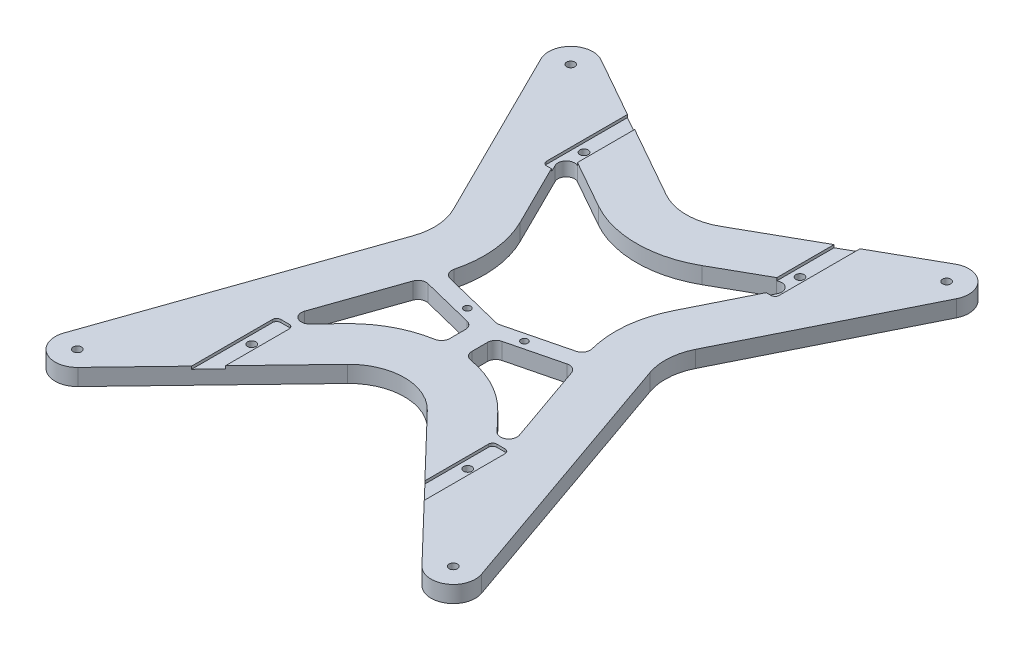
SolidWorks part; units mm, degrees
material "1060 Alloy"
ref_plane "Front Plane" through (0, 0, 0) normal (0, 0, 1) x (1, 0, 0)
ref_plane "Top Plane" through (0, 0, 0) normal (0, 1, 0) x (1, 0, 0)
ref_plane "Right Plane" through (0, 0, 0) normal (1, 0, 0) x (0, 0, -1)
sketch "Sketch1" plane through (0, 0, 0) normal (0, 1, 0) x (1, 0, 0)
  line L0 (-63.9527, 96.0638) -> (0, 60)
  line L1 (0, 60) -> (63.9527, 96.0638)
  line L2 (75.0466, 85.5357) -> (40, 15)
  line L3 (40, 15) -> (75.4349, -86.4576)
  line L4 (62.1139, -94.6385) -> (0, -30)
  line L5 (0, -30) -> (-62.1139, -94.6385)
  line L6 (-75.4349, -86.4576) -> (-40, 15)
  line L7 (-40, 15) -> (-75.0466, 85.5357)
  line L8 (-78.4889, 78.4889) -> (78.4889, -78.4889) construction
  line L9 (-42, 75) -> (-36, 75) construction
  line L10 (-42, 75) -> (-42, 55) construction
  line L11 (-42, 55) -> (-36, 55) construction
  line L12 (-36, 75) -> (-36, 55) construction
  line L13 (-42, 75) -> (-36, 55) construction
  line L14 (-42, 55) -> (-36, 75) construction
  line L15 (36, 75) -> (42, 75) construction
  line L16 (36, 75) -> (36, 55) construction
  line L17 (36, 55) -> (42, 55) construction
  line L18 (42, 75) -> (42, 55) construction
  line L19 (36, 75) -> (42, 55) construction
  line L20 (36, 55) -> (42, 75) construction
  line L21 (36, -45) -> (42, -45) construction
  line L22 (36, -45) -> (36, -65) construction
  line L23 (36, -65) -> (42, -65) construction
  line L24 (42, -45) -> (42, -65) construction
  line L25 (36, -45) -> (42, -65) construction
  line L26 (36, -65) -> (42, -45) construction
  line L27 (-42, -45) -> (-36, -45) construction
  line L28 (-42, -45) -> (-42, -65) construction
  line L29 (-42, -65) -> (-36, -65) construction
  line L30 (-36, -45) -> (-36, -65) construction
  line L31 (-42, -45) -> (-36, -65) construction
  line L32 (-42, -65) -> (-36, -45) construction
  line L33 (111, 45.9777) -> (45.9777, 111) construction
  line L34 (45.9777, 111) -> (-45.9777, 111) construction
  line L35 (-45.9777, 111) -> (-111, 45.9777) construction
  line L36 (-111, 45.9777) -> (-111, -45.9777) construction
  line L37 (-111, -45.9777) -> (-45.9777, -111) construction
  line L38 (-45.9777, -111) -> (45.9777, -111) construction
  line L39 (45.9777, -111) -> (111, -45.9777) construction
  line L40 (111, -45.9777) -> (111, 45.9777) construction
  line L41 (78.4889, 78.4889) -> (-78.4889, -78.4889) construction
  circle A0 centre (-67.8823, 89.0955) radius 1.5
  circle A1 centre (67.8823, 89.0955) radius 1.5
  circle A2 centre (-67.8823, -89.0955) radius 1.5
  circle A3 centre (67.8823, -89.0955) radius 1.5
  arc A4 (-63.9527, 96.0638) -> (-75.0466, 85.5357) centre (-67.8823, 89.0955) ccw
  arc A5 (63.9527, 96.0638) -> (75.0466, 85.5357) centre (67.8823, 89.0955) cw
  arc A6 (-75.4349, -86.4576) -> (-62.1139, -94.6385) centre (-67.8823, -89.0955) ccw
  arc A7 (75.4349, -86.4576) -> (62.1139, -94.6385) centre (67.8823, -89.0955) cw
  circle A8 centre (0, 0) radius 111 construction
  circle A9 centre (-39, 65) radius 1.5
  circle A10 centre (39, 65) radius 1.5
  circle A11 centre (39, -55) radius 1.5
  circle A12 centre (-39, -55) radius 1.5
  ellipse E0 centre (0, 15) end of major axis (0, 60) minor radius 40 construction
  dimension "D5" = 3
  dimension "D6" = 45
  dimension "D7" = 8
  dimension "D12" = 3
  dimension "D3" = 15
  dimension "D4" = 15
  dimension "D8" = 120
  dimension "D9" = 78
  dimension "D10" = 15
  dimension "D11" = 55
  dimension "D13" = 40
  dimension "D14" = 39
  dimension "D15" = 20
  dimension "D16" = 6
  dimension "D17" = 111
  dimension "D18" = 15
extrude "Boss-Extrude1" add sketch "Sketch1" along normal blind 6
fillet "Fillet1" radius 20 4 edges at (0, 3, -60) (-40, 3, -15) (0, 3, 30) (40, 3, -15)
sketch "Sketch2" plane through (0, 6, 0) normal (0, 1, 0) x (1, 0, 0)
  line L44 (-44.4448, 64.3983) -> (-27.6278, 30.5519)
  line L45 (-25.7837, 1.1137) -> (-43.3232, -49.1058)
  line L46 (-43.3232, -49.1058) -> (-27.3998, -32.5352)
  line L47 (27.3998, -32.5352) -> (43.3232, -49.1058)
  line L48 (43.3232, -49.1058) -> (25.7837, 1.1137)
  line L49 (27.6278, 30.5519) -> (44.4448, 64.3983)
  line L50 (44.4448, 64.3983) -> (18.6655, 49.861)
  line L51 (-18.6655, 49.861) -> (-44.4448, 64.3983)
  line L52 (-44.4448, 64.3983) -> (-27.6278, 30.5519)
  line L53 (-25.7837, 1.1137) -> (-43.3232, -49.1058)
  line L54 (-43.3232, -49.1058) -> (-27.3998, -32.5352)
  line L55 (27.3998, -32.5352) -> (43.3232, -49.1058)
  line L56 (43.3232, -49.1058) -> (25.7837, 1.1137)
  line L57 (27.6278, 30.5519) -> (44.4448, 64.3983)
  line L58 (44.4448, 64.3983) -> (18.6655, 49.861)
  line L59 (-18.6655, 49.861) -> (-44.4448, 64.3983)
  arc A40 (-25.7837, 1.1137) -> (-27.6278, 30.5519) centre (-61.6586, 13.6432) ccw
  arc A41 (27.3998, -32.5352) -> (-27.3998, -32.5352) centre (0, -58.8648) ccw
  arc A42 (27.6278, 30.5519) -> (25.7837, 1.1137) centre (61.6586, 13.6432) ccw
  arc A43 (-18.6655, 49.861) -> (18.6655, 49.861) centre (0, 82.9608) ccw
  arc A44 (-25.7837, 1.1137) -> (-27.6278, 30.5519) centre (-61.6586, 13.6432) ccw
  arc A45 (27.3998, -32.5352) -> (-27.3998, -32.5352) centre (0, -58.8648) ccw
  arc A46 (27.6278, 30.5519) -> (25.7837, 1.1137) centre (61.6586, 13.6432) ccw
  arc A47 (-18.6655, 49.861) -> (18.6655, 49.861) centre (0, 82.9608) ccw
  dimension "D1" = 18
extrude "Cut-Extrude1" cut sketch "Sketch2" against normal up to next
sketch "Sketch5" plane through (0, 6, 0) normal (0, 1, 0) x (1, 0, 0)
  line L0 (-26.3219, 1.2476) -> (0, -5.3011)
  line L1 (-12.94, -8.43) -> (12.94, -8.43) construction
  line L2 (-12.94, -8.43) -> (-12.94, 8.43) construction
  line L3 (-12.94, 8.43) -> (12.94, 8.43) construction
  line L4 (12.94, -8.43) -> (12.94, 8.43) construction
  line L5 (-12.94, -8.43) -> (12.94, 8.43) construction
  line L6 (-12.94, 8.43) -> (12.94, -8.43) construction
  line L7 (-25.7837, 1.1137) -> (-43.3232, -49.1058) construction
  line L8 (0, -5.3011) -> (26.3219, 1.2476)
  line L9 (43.3232, -49.1058) -> (25.7837, 1.1137) construction
  line L10 (26.3219, 1.2476) -> (27.7705, -4.5749)
  line L11 (27.7705, -4.5749) -> (4, -10.4888)
  line L12 (4, -10.4888) -> (4, -21.0759)
  line L13 (-4, -21.0759) -> (-4, -10.4888)
  line L14 (-4, -10.4888) -> (-27.7705, -4.5749)
  line L15 (-27.7705, -4.5749) -> (-26.3219, 1.2476)
  line L16 (43.3232, -49.1058) -> (25.7837, 1.1137) construction
  circle A0 centre (-10.3, -5.83) radius 1.25
  circle A1 centre (10.3, -5.83) radius 1.25
  arc A2 (27.3998, -32.5352) -> (-27.3998, -32.5352) centre (0, -58.8648) ccw construction
  arc A3 (4, -21.0759) -> (-4, -21.0759) centre (0, -58.8648) ccw
  point P0 (0, 0)
  dimension "D3" = 2.5
  dimension "D1" = 16.86
  dimension "D2" = 25.88
  dimension "D4" = 20.6
  dimension "D5" = 2.64
  dimension "D6" = 2.6
  dimension "D7" = 6
  dimension "D8" = 3
  dimension "D9" = 8
extrude "Boss-Extrude2" add sketch "Sketch5" against normal up to surface (6 mm away) up to face at (0, 0, -11.3092)
fillet "Fillet2" radius 3 13 edges at (43.3232, 3, 49.1058) (-43.3232, 3, 49.1058) (44.4448, 3, -64.3983) (-44.4448, 3, -64.3983) (0, 3, 5.3011) (27.7705, 3, 4.5749) (4, 3, 10.4888) (4, 3, 21.0759) (-4, 3, 21.0759) (-4, 3, 10.4888) (-27.7705, 3, 4.5749) (25.7837, 3, -1.1137) (-25.7837, 3, -1.1137)
sketch "Sketch6" plane through (0, 6, 0) normal (0, 1, 0) x (1, 0, 0)
  line L0 (-9.8239, 65.5399) -> (-63.9527, 96.0638) construction
  line L1 (-42, -43) -> (-36, -43)
  line L2 (-42, -43) -> (-42, -73.7071)
  line L3 (-42, -73.7071) -> (-36, -73.7071)
  line L4 (-36, -43) -> (-36, -73.7071)
  line L5 (36, -43) -> (42, -43)
  line L6 (36, -43) -> (36, -73.7071)
  line L7 (36, -73.7071) -> (42, -73.7071)
  line L8 (42, -43) -> (42, -73.7071)
  line L9 (36, 53) -> (42, 53)
  line L10 (36, 53) -> (36, 83.6844)
  line L11 (36, 83.6844) -> (42, 83.6844)
  line L12 (42, 53) -> (42, 83.6844)
  line L13 (-42, 53) -> (-36, 53)
  line L14 (-42, 53) -> (-42, 83.6844)
  line L15 (-42, 83.6844) -> (-36, 83.6844)
  line L16 (-36, 53) -> (-36, 83.6844)
  line L17 (63.9527, 96.0638) -> (9.8239, 65.5399) construction
  line L18 (14.421, -45.0071) -> (62.1139, -94.6385) construction
  line L19 (-62.1139, -94.6385) -> (-14.421, -45.0071) construction
  circle A0 centre (-39, -55) radius 1.5 construction
  circle A1 centre (39, -55) radius 1.5 construction
  circle A2 centre (-39, 65) radius 1.5 construction
  dimension "D2" = 3
  dimension "D3" = 3
  dimension "D5" = 12
  dimension "D1" = 6
  dimension "D4" = 12
extrude "Cut-Extrude2" cut sketch "Sketch6" against normal blind 1
fillet "Fillet3" radius 1.5 6 edges at (-42, 5.5, -53) (42, 5.5, -53) (36, 5.5, 43) (42, 5.5, 43) (-36, 5.5, 43) (-42, 5.5, 43)
equation "\"D14@Sketch1\"=\"D9@Sketch1\"/2"
